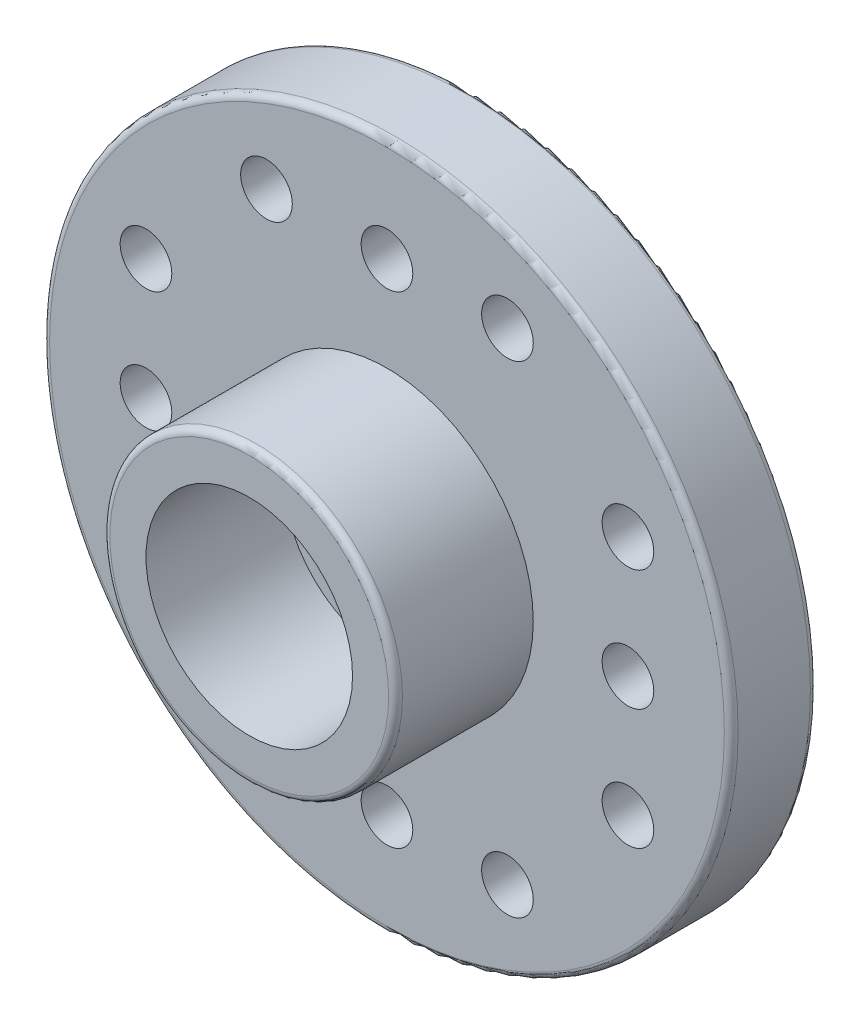
SolidWorks part; units mm, degrees
ref_plane "Front Plane" through (0, 0, 0) normal (0, 0, 1) x (1, 0, 0)
ref_plane "Top Plane" through (0, 0, 0) normal (0, 1, 0) x (1, 0, 0)
ref_plane "Right Plane" through (0, 0, 0) normal (1, 0, 0) x (0, 0, -1)
sketch "Sketch1" plane through (0, 0, 0) normal (0, 0, 1) x (1, 0, 0)
  line L0 (-7, 3.5) -> (-7, -3.5) construction
  line L1 (-7, 0) -> (0, 0) construction
  circle A0 centre (0, 0) radius 10
  circle A1 centre (-7, 0) radius 0.75
  circle A2 centre (3.5, 7) radius 0.75
  circle A3 centre (0, 7) radius 0.75
  circle A4 centre (-3.5, 7) radius 0.75
  circle A5 centre (7, -3.5) radius 0.75
  circle A6 centre (7, 0) radius 0.75
  circle A7 centre (7, 3.5) radius 0.75
  circle A8 centre (-3.5, -7) radius 0.75
  circle A9 centre (0, -7) radius 0.75
  circle A10 centre (3.5, -7) radius 0.75
  circle A11 centre (-7, -3.5) radius 0.75
  circle A13 centre (-7, 3.5) radius 0.75
  circle A22 centre (0, 0) radius 1.5
  point P25 (0, 0)
  dimension "D2" = 20
  dimension "D4" = 7
  dimension "D5" = 3.5
  dimension "D14" = 3
  dimension "D6" = 3.5
  dimension "D3" = 1.5
extrude "Boss-Extrude1" add sketch "Sketch1" along normal blind 2.5
sketch "Sketch5" plane through (0, 0, 2.5) normal (0, 0, 1) x (1, 0, 0)
  circle A0 centre (0, 0) radius 3
  circle A1 centre (0, 0) radius 4.25
  dimension "D1" = 8.5
  dimension "D2" = 6
extrude "Boss-Extrude2" add sketch "Sketch5" along normal blind 4
sketch "Sketch6" plane through (0, 0, 0) normal (0, 0, -1) x (-1, 0, 0)
  circle A0 centre (0, 0) radius 3.5
  dimension "D1" = 7
extrude "Cut-Extrude1" cut sketch "Sketch6" against normal blind 0.8
fillet "Fillet1" radius 0.2 4 edges at (10, 0, 0) (10, 0, 2.5) (-3.5, 0, 0) (4.25, 0, 6.5)
